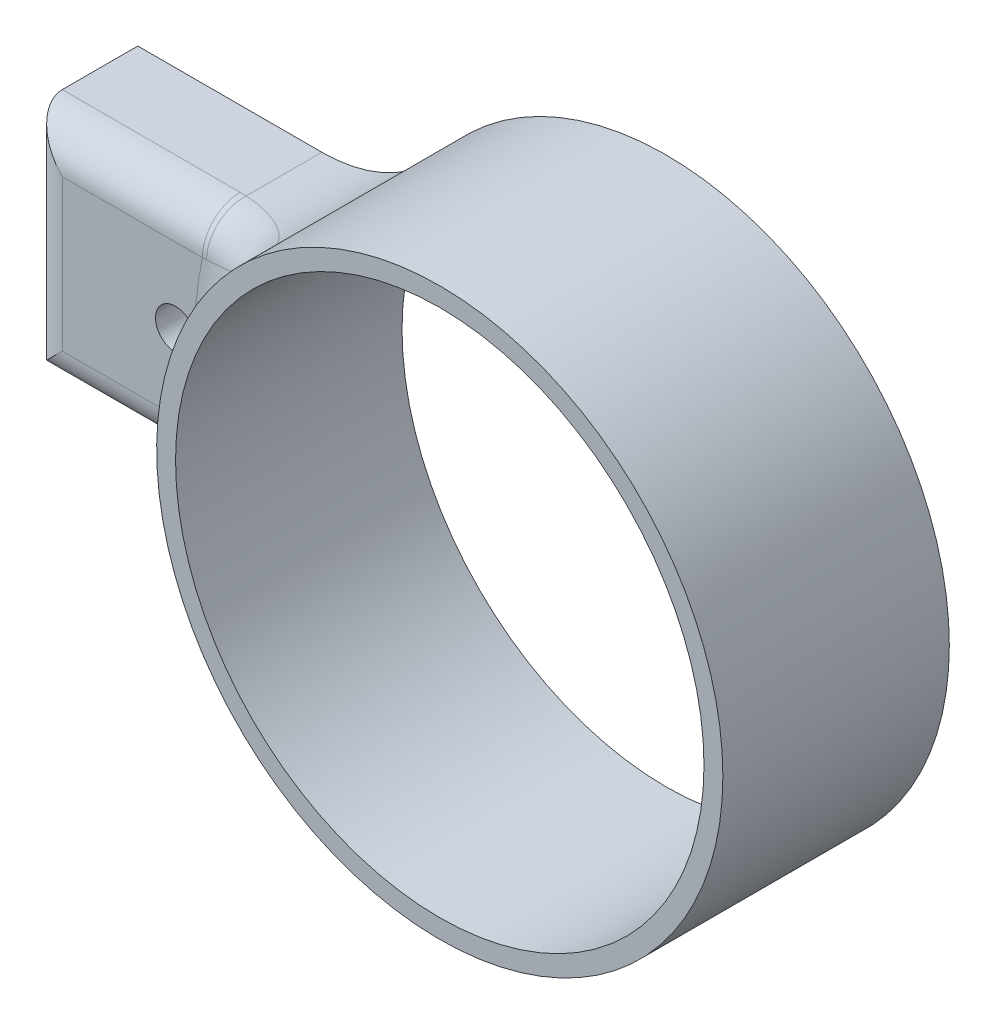
SolidWorks part; units mm, degrees
ref_plane "Plan de face" through (0, 0, 0) normal (0, 0, 1) x (1, 0, 0)
ref_plane "Plan de dessus" through (0, 0, 0) normal (0, 1, 0) x (1, 0, 0)
ref_plane "Plan de droite" through (0, 0, 0) normal (1, 0, 0) x (0, 0, -1)
sketch "Esquisse5" plane through (0, 0, 0) normal (0, 0, 1) x (1, 0, 0)
  line L0 (-1000, 0) -> (49000, 0) construction
  line L1 (-45.6207, 15) -> (-70, 15)
  line L2 (-70, 15) -> (-70, -15)
  line L3 (-45.6207, -15) -> (-70, -15)
  circle A0 centre (0, 0) radius 35
  arc A1 (-29.7526, -22.8261) -> (-29.7526, 22.8261) centre (0, 0) ccw
  arc A2 (-45.6207, 15) -> (-29.7526, 22.8261) centre (-45.6207, 35) ccw
  arc A3 (-45.6207, -15) -> (-29.7526, -22.8261) centre (-45.6207, -35) cw
  point P14 (-70, 0)
  dimension "D1" = 70
  dimension "D2" = 75
  dimension "D5" = 20
  dimension "D3" = 15
  dimension "D4" = 70
extrude "Boss.-Extru.4" add sketch "Esquisse5" along normal blind 15
sketch "Esquisse8" plane through (0, 0, 15) normal (0, 0, 1) x (1, 0, 0)
  circle A0 centre (0, 0) radius 35
  circle A1 centre (0, 0) radius 37.5
  circle A2 centre (0, 0) radius 35 construction
  arc A3 (-29.7526, -22.8261) -> (-29.7526, 22.8261) centre (0, 0) ccw construction
extrude "Boss.-Extru.7" add sketch "Esquisse8" along normal blind 15
fillet "Congé3" radius 10 1 edges at (-37.5, 0, 15)
fillet "Congé4" radius 5 7 edges at (-45.3438, 15.0019, 15) (-45.3438, -15.0019, 15) (-36.9031, 16.9999, 17.733) (-57.8104, 15, 15) (-70, 0, 15) (-57.8104, -15, 15) (-36.9031, -16.9999, 17.733)
sketch "Esquisse12" plane through (-70, 0, 0) normal (-1, 0, 0) x (0, 0, 1)
  line L5 (0, 10) -> (10, 10) construction
  line L8 (0, 15) -> (0, -15) construction
  line L9 (10, 10) -> (10, -10) construction
  line L10 (-1000, 0) -> (49000, 0) construction
  line L11 (0, -10) -> (10, -10) construction
  line L12 (10, 15) -> (0, 15) construction
  line L14 (0, 10) -> (0, -10) construction
  line L15 (-0.2, 10.2) -> (10.2, 10.2)
  line L16 (10.2, 10.2) -> (10.2, -10.2)
  line L17 (-0.2, -10.2) -> (10.2, -10.2)
  line L18 (-0.2, 10.2) -> (-0.2, -10.2)
  line L20 (15, -10) -> (15, 10) construction
  point P9 (10, 0)
  dimension "D1" = 5
  dimension "D2" = 5
  dimension "D3" = 0.2
extrude "Enlèv. mat.-Extru.2" cut sketch "Esquisse12" against normal blind 25
sketch "Esquisse13" plane through (0, 0, 15) normal (0, 0, 1) x (1, 0, 0)
  line L0 (-69.996, -10.2) -> (-69.996, 10.2) construction
  circle A0 centre (-49.996, 0) radius 2.65
  dimension "D1" = 5.3
  dimension "D2" = 20
extrude "Enlèv. mat.-Extru.3" cut sketch "Esquisse13" against normal up to next and the other way through all
